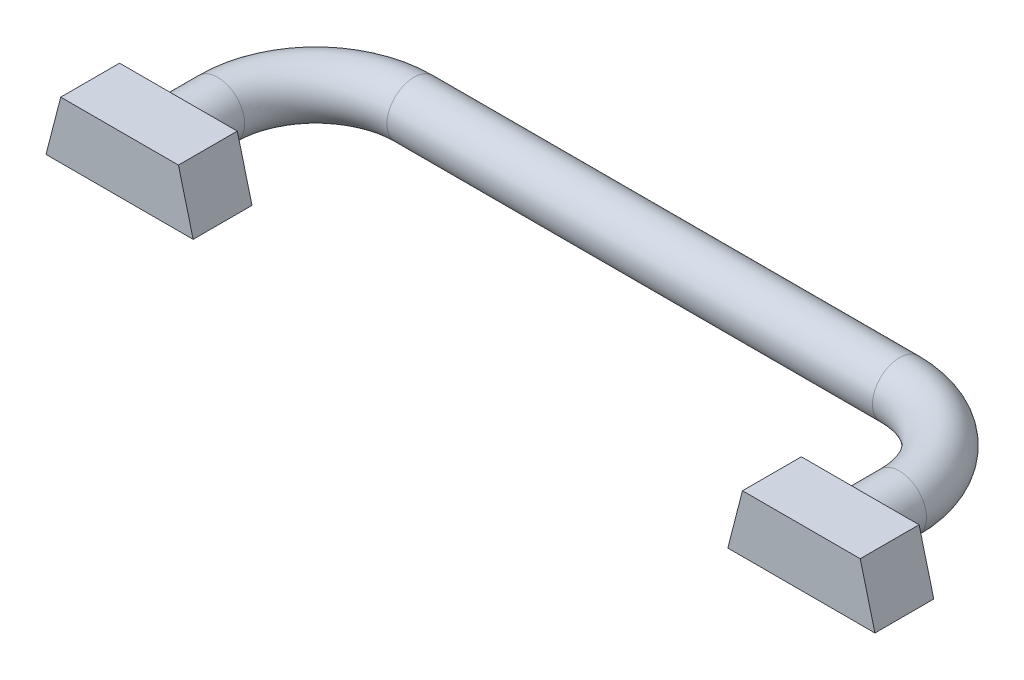
SolidWorks part; units mm, degrees
ref_plane "Спереди" through (0, 0, 0) normal (0, 0, 1) x (1, 0, 0)
ref_plane "Сверху" through (0, 0, 0) normal (0, 1, 0) x (1, 0, 0)
ref_plane "Справа" through (0, 0, 0) normal (1, 0, 0) x (0, 0, -1)
sketch "Эскиз1" plane through (0, 0, 0) normal (0, 1, 0) x (1, 0, 0)
  line L0 (0, 0) -> (0, 10)
  line L1 (10, 20) -> (59.5, 20)
  line L2 (69.5, 10) -> (69.5, 0)
  arc A0 (10, 20) -> (0, 10) centre (10, 10) ccw
  arc A1 (69.5, 10) -> (59.5, 20) centre (59.5, 10) ccw
  point P7 (0, 20)
  point P10 (69.5, 20)
  dimension "D4" = 10
  dimension "D5" = 10
  dimension "D1" = 20
  dimension "D2" = 69.5
  dimension "D3" = 20
sketch "Эскиз2" plane through (0, 0, 0) normal (0, 0, 1) x (1, 0, 0)
  circle A0 centre (0, 0) radius 2.75
  dimension "D1" = 5.5
sweep "По траектории1" add profiles "Эскиз2" path "Эскиз1"
sketch "Эскиз3" plane through (0, 0, 0) normal (0, 0, 1) x (1, 0, 0)
  line L0 (0, 0) -> (0, 6.3701) construction
  line L1 (-6, 3) -> (6, 3)
  line L2 (6, 3) -> (7.5, -2.8095)
  line L3 (7.5, -2.8095) -> (-7.5, -2.8095)
  line L4 (-7.5, -2.8095) -> (-6, 3)
  point P7 (0, 3)
  point P8 (0, 0)
  point P9 (0, -2.8095)
  point P10 (0, 0)
  dimension "D1" = 15
  dimension "D2" = 12
  dimension "D3" = 6
  dimension "D4" = 3
extrude "Бобышка-Вытянуть1" add sketch "Эскиз3" against normal blind 6
sketch "Эскиз4" plane through (0, 0, 0) normal (0, 0, 1) x (1, 0, 0)
  line L0 (69.5, 0) -> (69.5, 6.0342) construction
  line L1 (63.5, 3) -> (75.5, 3)
  line L2 (75.5, 3) -> (77, -2.8095)
  line L3 (77, -2.8095) -> (62, -2.8095)
  line L4 (62, -2.8095) -> (63.5, 3)
  point P7 (69.5, -2.8095)
  point P8 (69.5, 3)
  point P9 (0, 0)
  dimension "D1" = 3
  dimension "D2" = 12
  dimension "D3" = 15
  dimension "D4" = 6
extrude "Бобышка-Вытянуть2" add sketch "Эскиз4" against normal blind 6
